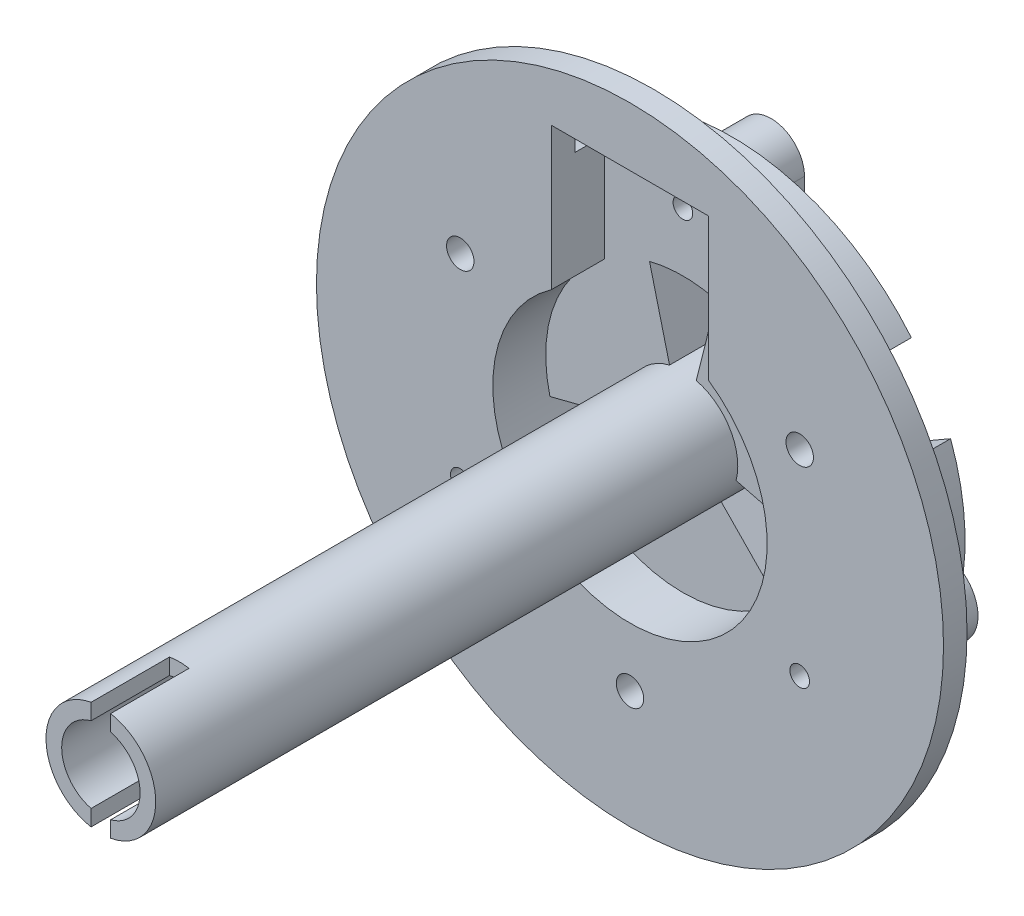
SolidWorks part; units mm, degrees
ref_plane "前视基准面" through (0, 0, 0) normal (0, 0, 1) x (1, 0, 0)
ref_plane "上视基准面" through (0, 0, 0) normal (0, 1, 0) x (1, 0, 0)
ref_plane "右视基准面" through (0, 0, 0) normal (1, 0, 0) x (0, 0, -1)
sketch "草图1" plane through (0, 0, 0) normal (0, 0, 1) x (1, 0, 0)
  circle A0 centre (0, 0) radius 16
extrude "凸台-拉伸1" add sketch "草图1" along normal blind 1.2
sketch "草图2" plane through (0, 0, 1.2) normal (0, 0, 1) x (1, 0, 0)
  circle A0 centre (0, 0) radius 7
extrude "切除-拉伸1" cut sketch "草图2" against normal blind 1.2
sketch "草图3" plane through (0, 0, 1.2) normal (0, 0, 1) x (1, 0, 0)
  circle A2 centre (8.6603, 5) radius 0.7
  circle A3 centre (0, -10) radius 0.7
  circle A4 centre (-8.6603, 5) radius 0.7
extrude "切除-拉伸2" cut sketch "草图3" against normal blind 1.2
sketch "草图4" plane through (0, 0, 0) normal (0, 0, -1) x (-1, 0, 0)
  line L3 (1.7039, 10) -> (1.7039, 5.3952)
  line L16 (-5.5379, -1.0034) -> (-3.6379, -4.2943)
  line L17 (3.6379, -4.2943) -> (5.5379, -1.0034)
  line L18 (1.7039, 5.3952) -> (-1.7039, 5.3952)
  line L19 (-5.5379, -1.0034) -> (-9.6103, -3.3546)
  line L21 (3.6379, -4.2943) -> (7.7103, -6.6454)
  line L25 (-3.6379, -4.2943) -> (-7.7103, -6.6454)
  line L31 (5.5379, -1.0034) -> (9.6103, -3.3546)
  line L32 (-1.7039, 5.3952) -> (-1.7039, 10)
  circle A1 centre (8.6603, -5) radius 0.9
  circle A2 centre (-8.6603, -5) radius 0.9
  circle A3 centre (0, 10) radius 0.9
  arc A4 (1.7039, 10) -> (-1.7039, 10) centre (0, 10) ccw
  arc A5 (7.7103, -6.6454) -> (9.6103, -3.3546) centre (8.6603, -5) ccw
  arc A6 (-9.6103, -3.3546) -> (-7.7103, -6.6454) centre (-8.6603, -5) ccw
extrude "凸台-拉伸2" add sketch "草图4" along normal blind 6
sketch "草图5" plane through (0, 0, 1.2) normal (0, 0, 1) x (1, 0, 0)
  circle A0 centre (0, 0) radius 7
extrude "切除-拉伸3" cut sketch "草图5" against normal blind 11
sketch "草图6" plane through (0, 0, 0) normal (0, 0, -1) x (-1, 0, 0)
  circle A0 centre (0, 0) radius 11.9
  circle A1 centre (0, 0) radius 7
extrude "凸台-拉伸3" add sketch "草图6" along normal blind 4
sketch "草图7" plane through (0, 0, 1.2) normal (0, 0, 1) x (1, 0, 0)
  circle A0 centre (-8.6603, 5) radius 0.7
  circle A1 centre (8.6603, 5) radius 0.7
  circle A2 centre (0, -10) radius 0.7
extrude "切除-拉伸4" cut sketch "草图7" against normal blind 13
sketch "草图8" plane through (0, 0, -4) normal (0, 0, -1) x (-1, 0, 0)
  circle A0 centre (0, 0) radius 2.8
extrude "凸台-拉伸4" add sketch "草图8" against normal blind 33 separate body
sketch "草图9" plane through (0, 0, -4) normal (0, 0, -1) x (-1, 0, 0)
  line L0 (-1.57, -1.6117) -> (-4.8846, -5.0141)
  line L1 (1.57, -1.6117) -> (4.8846, -5.0141)
  line L2 (-2.1808, -0.5539) -> (-6.7846, -1.7232)
  line L3 (-0.5477, 2.1823) -> (-1.7039, 6.7895)
  line L4 (0.5477, 2.1823) -> (1.7039, 6.7895)
  line L5 (2.1808, -0.5539) -> (6.7846, -1.7232)
  arc A0 (-4.8846, -5.0141) -> (4.8846, -5.0141) centre (0, 0) ccw
  arc A1 (-1.7039, 6.7895) -> (-6.7846, -1.7232) centre (0, 0) ccw
  arc A2 (6.7846, -1.7232) -> (1.7039, 6.7895) centre (0, 0) ccw
  arc A3 (2.1808, -0.5539) -> (0.5477, 2.1823) centre (0, 0) ccw
  arc A4 (-1.57, -1.6117) -> (1.57, -1.6117) centre (0, 0) ccw
  arc A5 (-0.5477, 2.1823) -> (-2.1808, -0.5539) centre (0, 0) ccw
extrude "凸台-拉伸5" add sketch "草图9" against normal blind 2.5
sketch "草图10" plane through (0, 0, -4) normal (0, 0, -1) x (-1, 0, 0)
  circle A0 centre (0, 0) radius 1.5
extrude "切除-拉伸5" cut sketch "草图10" against normal blind 33.5
sketch "草图12" plane through (0, 0, 0) normal (1, 0, 0) x (0, 0, -1)
  line L3 (-19.95, -5.0897) -> (-33.7637, -5.0897)
  line L4 (-19.95, -5.0897) -> (-19.95, 5.3715)
  line L5 (-19.95, 5.3715) -> (-33.7637, 5.3715)
  line L6 (-33.7637, -5.0897) -> (-33.7637, 5.3715)
extrude "切除-拉伸6" cut sketch "草图12" against normal mid plane 33.5
sketch "草图13" plane through (0, 0, -4) normal (0, 0, -1) x (-1, 0, 0)
  circle A0 centre (0, -10) radius 2
  circle A1 centre (8.6603, 5) radius 2
  circle A2 centre (-8.6603, 5) radius 2
extrude "切除-拉伸7" cut sketch "草图13" against normal blind 1.5
sketch "草图14" plane through (0, 0, 19.95) normal (0, 0, 1) x (1, 0, 0)
  circle A0 centre (0, 0) radius 2
  circle A1 centre (0, 0) radius 2.8
extrude "凸台-拉伸6" add sketch "草图14" along normal blind 8.25
sketch "草图16" plane through (0, 0, -4) normal (0, 0, -1) x (-1, 0, 0)
  line L3 (0, -10) -> (-2, -10)
  line L4 (-2, -10) -> (-2, -14.1303)
  line L5 (-2, -14.1303) -> (2, -14.1303)
  line L6 (2, -14.1303) -> (2, -10)
  line L7 (2, -10) -> (0, -10)
  line L8 (-9.6603, 3.2679) -> (-8.6603, 5)
  line L9 (-8.6603, 5) -> (-7.6603, 6.7321)
  line L10 (-7.6603, 6.7321) -> (-11.2372, 8.7972)
  line L11 (-11.2372, 8.7972) -> (-13.2372, 5.3331)
  line L12 (-13.2372, 5.3331) -> (-9.6603, 3.2679)
  line L13 (7.6603, 6.7321) -> (8.6603, 5)
  line L14 (8.6603, 5) -> (9.6603, 3.2679)
  line L15 (9.6603, 3.2679) -> (13.2372, 5.3331)
  line L16 (13.2372, 5.3331) -> (11.2372, 8.7972)
  line L17 (11.2372, 8.7972) -> (7.6603, 6.7321)
  arc A0 (0.681, -11.8805) -> (-0.681, -11.8805) centre (0, -10) ccw construction
  arc A1 (0.681, -11.8805) -> (-0.681, -11.8805) centre (0, -10) ccw construction
  point P26 (0, 0)
  dimension "D1" = 3
extrude "切除-拉伸9" cut sketch "草图16" against normal blind 1.5
sketch "草图17" plane through (0, 0, 28.2) normal (0, 0, 1) x (1, 0, 0)
  circle A0 centre (0, 0) radius 1.5
  circle A1 centre (0, 0) radius 1.48
extrude "凸台-拉伸7" add sketch "草图17" against normal blind 32.2
sketch "草图15" plane through (0, 0, 28.2) normal (0, 0, 1) x (1, 0, 0)
  line L2 (0.5, 0) -> (0.5, 3.0915)
  line L3 (0.5, 3.0915) -> (-0.5, 3.0915)
  line L4 (-0.5, 3.0915) -> (-0.5, -2.9006)
  line L5 (-0.5, -2.9006) -> (0.5, -2.9006)
  line L6 (0.5, -2.9006) -> (0.5, 0)
extrude "切除-拉伸8" cut sketch "草图15" against normal blind 4
sketch "草图18" plane through (0, 0, 1.2) normal (0, 0, 1) x (1, 0, 0)
  line L0 (0, 13) -> (-4, 13)
  line L2 (-4, 13) -> (-4, 4.7297)
  line L3 (-4, 4.7297) -> (4, 4.7297)
  line L4 (4, 4.7297) -> (4, 13)
  line L5 (4, 13) -> (0, 13)
extrude "切除-拉伸10" cut sketch "草图18" against normal blind 2.7
sketch "草图19" plane through (0, 0, -6) normal (0, 0, -1) x (-1, 0, 0)
  circle A0 centre (-8.6603, -5) radius 0.5
  circle A1 centre (0, 10) radius 0.5
  circle A2 centre (8.6603, -5) radius 0.5
extrude "切除-拉伸11" cut sketch "草图19" against normal blind 10
sketch "草图20" plane through (0, 0, 28.2) normal (0, 0, 1) x (1, 0, 0)
  circle A0 centre (0, 0) radius 2
extrude "切除-拉伸12" cut sketch "草图20" against normal blind 45
